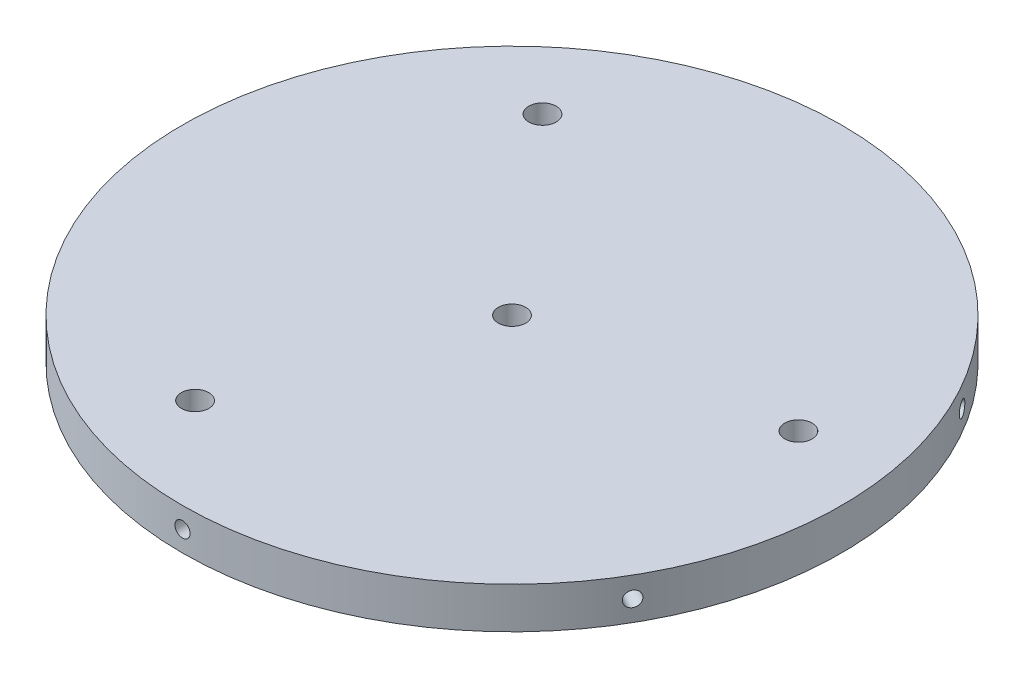
SolidWorks part; units mm, degrees
ref_plane "Front Plane" through (0, 0, 0) normal (0, 0, 1) x (1, 0, 0)
ref_plane "Top Plane" through (0, 0, 0) normal (0, 1, 0) x (1, 0, 0)
ref_plane "Right Plane" through (0, 0, 0) normal (1, 0, 0) x (0, 0, -1)
sketch "Sketch1" plane through (0, 0, 0) normal (0, 1, 0) x (1, 0, 0)
  line L0 (0, 0) -> (-50.3682, 60.0265)
  line L1 (0, 0) -> (50.3682, 60.0265)
  line L2 (0, 0) -> (0, 72.1431) construction
  circle A0 centre (0, 0) radius 78.359
  circle A1 centre (0, 0) radius 76.1746
  circle A2 centre (0, 0) radius 76.1746
  dimension "D1" = 156.718
  dimension "D2" = 152.3492
  dimension "D3" = 152.3492
  dimension "D4" = 80
extrude "Boss-Extrude1" add sketch "Sketch1" along normal blind 25.4 contours L2 A2 L1 A0 | L2 A1 L1 A2 | L2 A2 L1 A1 | L2 A0 L1 A2 | A2 L2 A1 L0 | A0 L2 A2 L0 | A2 L2 A0 L0 | A1 L2 A2 L0 region at (0, 0, 13.3592) region at (-23.5316, 0, -29.974) region at (-33.0764, 0, 70.9325) region at (-48.8794, 0, -59.85)
ref_plane "Plane1" through (0, 12.7, 0) normal (0, 1, 0) x (1, 0, 0)
sketch "Sketch6" plane through (0, 25.4, 0) normal (0, 1, 0) x (1, 0, 0)
  circle A0 centre (0, 0) radius 76.1746
  dimension "D1" = 152.3492
extrude "Boss-Extrude5" add sketch "Sketch6" along normal blind 9.525
sketch "Sketch7" plane through (0, 0, 0) normal (0, -1, 0) x (1, 0, 0)
  circle A0 centre (0, 0) radius 76.1746
  dimension "D1" = 152.3492
extrude "Boss-Extrude6" add sketch "Sketch7" along normal blind 9.525
sketch "Sketch8" plane through (0, -9.525, 0) normal (0, -1, 0) x (1, 0, 0)
  circle A0 centre (0, 0) radius 73.025
  dimension "D1" = 146.05
extrude "Cut-Extrude5" cut sketch "Sketch8" against normal up to surface (34.925 mm away) up to face at (0, 25.4, 76.1746)
ref_plane "Plane2" through (0, 0, -76.1746) normal (0, 0, -1) x (-1, 0, 0)
ref_plane "Plane5" through (0, 25.4, 0) normal (0, 1, 0) x (1, 0, 0)
ref_axis "Axis1" through (0, 0, 0) along (0, 1, 0)
sketch "Sketch3" plane through (0, 0, -76.1746) normal (0, 0, -1) x (-1, 0, 0)
  line L4 (76.1746, 0) -> (-76.1746, 0)
  line L5 (-76.1746, -9.525) -> (76.1746, -9.525)
  line L6 (76.1746, 25.4) -> (-76.1746, 25.4)
  line L7 (76.1746, 34.925) -> (-76.1746, 34.925)
  line L8 (0, 34.925) -> (0, 25.4) construction
  line L9 (0, 0) -> (0, -9.525) construction
  circle A0 centre (0, 30.1625) radius 1.75
  circle A1 centre (0, -4.7625) radius 1.75
  point P12 (0, 30.1625)
  point P13 (0, -4.7625)
  point P14 (-77.5445, 179.1871)
  dimension "D1" = 3.5
extrude "Cut-Extrude2" cut sketch "Sketch3" against normal blind 9.525 contours L8 A0 | L8 A0 | L9 A1 | L9 A1 region at (0, 30.1625, -76.1746) region at (0, -4.7625, -76.1746)
extrude "Cut-Extrude3" cut sketch "Sketch1<7>" against normal blind 9.525 from surface contours L2 A1 L1 A2 | A1 L2 A2 L0 | A2 L2 A0 L0 | L2 A2 L1 A0 region at (-23.5316, 0, -29.974) region at (-48.8794, 0, -59.85) starting at plane "Plane5"
sketch "Sketch1<7>" plane through (0, 0, 0) normal (0, 1, 0) x (1, 0, 0) same geometry as "Sketch1"
pattern_circular "CirPattern2" count 3 over 360 about axis through (0, 0, 0) along (0, 1, 0) of "Cut-Extrude3"
ref_plane "Plane3" through (0, 34.925, 0) normal (0, 1, 0) x (1, 0, 0)
sketch "Sketch4" plane through (0, 34.925, 0) normal (0, 1, 0) x (1, 0, 0)
  circle A0 centre (0, 0) radius 73.025
  dimension "D1" = 146.05
extrude "Boss-Extrude4" add sketch "Sketch4" against normal blind 9.525
pattern_circular "CirPattern3" count 6 over 360 about axis through (0, 0, 0) along (0, 1, 0) of "Cut-Extrude2"
sketch "Sketch9" plane through (0, 34.925, 0) normal (0, 1, 0) x (1, 0, 0)
  line L0 (0, 0) -> (-26.8004, -73.6334) construction
  circle A0 centre (0, 0) radius 3.175
  circle A1 centre (-19.5465, -53.7034) radius 3.175
  circle A2 centre (-36.7353, 43.7794) radius 3.175
  circle A3 centre (56.2818, 9.924) radius 3.175
  point P15 (0, 0)
  dimension "D1" = 6.35
  dimension "D2" = 6.35
  dimension "D3" = 57.15
  dimension "D5" = 3
extrude "Cut-Extrude6" cut sketch "Sketch9" against normal through all
sketch "Sketch10" plane through (0, 25.4, 0) normal (0, 1, 0) x (1, 0, 0)
  circle A0 centre (0, 0) radius 82.3228
extrude "Cut-Extrude7" cut sketch "Sketch10" against normal through all
equation "\"AB_Coupler_OD_Length\"= 1in"
equation "\"AB_Coupling_Section_Length\"= 0.375in"
equation "\"AB_Coupler_Length\"= \"AB_Coupler_OD_Length\" + \"AB_Coupling_Section_Length\" * 2"
equation "\"Cutout_Angle\" = 80"
equation "\"AB_Coupler_Num_Screws\"= 6"
equation "\"Num_Cutouts\" = 3"
equation "\"AB_Coupler_OD\"= 6.17in"
equation "\"AB_Coupler_ID\"= 5.75in"
equation "\"AB_Coupler_Surface_Diameter\"= 5.998in"
equation "\"D2@Sketch1\"=\"Bodytube_ID\""
equation "\"AB_Coupling_Screw_Diameter\"= 0.1065in"
equation "\"Aft_Section_Length\"= 40in"
equation "\"Aft_Lower_Length\"= 22in"
equation "\"Aft_Upper_Length\"= \"Aft_Section_Length\" - \"Aft_Lower_Length\" - \"AB_Coupler_OD_Length\""
equation "\"Mid_Coupler_Length\" = 13in"
equation "\"Lead_Screw_Dist\" = 2.25in"
equation "\"Lead_Screw_Diam\" = (27/64)*1in"
equation "\"Lead_Screw_Length\" = (\"Mid_Coupler_Length\" + 2*0.375in + 2*0.5in)"
equation "\"Bodytube_OD\" = 6.17in"
equation "\"Paddle_Pin_Offset\" = .25in"
equation "\"Bodytube_ID\" = 5.998in"
equation "\"Paddle_Pin_Radius\" = 2.25in"
equation "\"D1@Sketch4\"=\"AB_Coupler_ID\""
equation "\"D1@Sketch6\"=\"AB_Coupler_Surface_Diameter\""
equation "\"D1@Boss-Extrude5\"=\"AB_Coupling_Section_Length\""
equation "\"D1@Sketch7\"=\"AB_Coupler_Surface_Diameter\""
equation "\"D1@Boss-Extrude6\"=\"AB_Coupling_Section_Length\""
equation "\"D1@Sketch8\"=\"AB_Coupler_ID\""
equation "\"D3@Sketch9\"=\"Paddle_Pin_Radius\""
